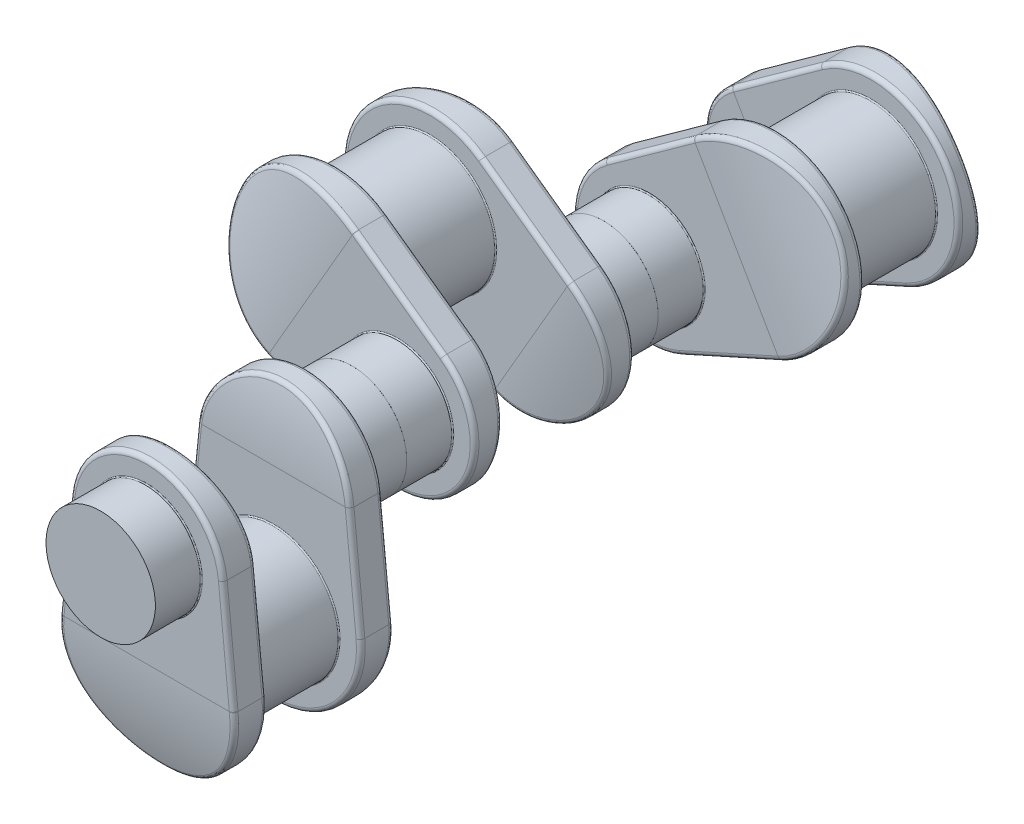
SolidWorks part; units mm, degrees
ref_plane "Front Plane" through (0, 0, 0) normal (0, 0, 1) x (1, 0, 0)
ref_plane "Top Plane" through (0, 0, 0) normal (0, 1, 0) x (1, 0, 0)
ref_plane "Right Plane" through (0, 0, 0) normal (1, 0, 0) x (0, 0, -1)
sketch "Sketch1" plane through (0, 0, 0) normal (0, 0, 1) x (1, 0, 0)
  circle A0 centre (0, 0) radius 38.1
extrude "Boss-Extrude1" add sketch "Sketch1" along normal blind 27.3
sketch "Sketch3" plane through (0, 0, 27.3) normal (0, 0, 1) x (1, 0, 0)
  line L0 (-44.2272, 67.945) -> (-50.5454, 5.08)
  line L1 (44.2272, 67.945) -> (50.5454, 5.08)
  arc A0 (-50.5454, 5.08) -> (50.5454, 5.08) centre (0, 0) ccw
  arc A1 (44.2272, 67.945) -> (-44.2272, 67.945) centre (0, 63.5) ccw
  circle A2 centre (0, 0) radius 38.1 construction
  dimension "D1" = 12.7
  dimension "D3" = 88.9
  dimension "D2" = 63.5
extrude "Boss-Extrude2" add sketch "Sketch3" along normal blind 19
sketch "Sketch4" plane through (0, 0, 46.3) normal (0, 0, 1) x (1, 0, 0)
  circle A0 centre (0, 63.5) radius 31.75
  dimension "D1" = 63.5
extrude "Boss-Extrude3" add sketch "Sketch4" along normal blind 26.67
sketch "Sketch7" plane through (0, 0, 0) normal (1, 0, 0) x (0, 0, -1)
  line L0 (-46.3, -50.8) -> (-27.3, -50.8) construction
  line L1 (-46.3, 5.08) -> (-70.3889, 5.08)
  line L2 (-70.3889, 5.08) -> (-70.3889, -50.8)
  line L3 (-70.3889, -50.8) -> (-36.8, -50.8)
  arc A0 (-46.3, 5.08) -> (-36.8, -50.8) centre (122.7, 5.0637) ccw
  dimension "D1" = 169
extrude "Cut-Extrude1" cut sketch "Sketch7" against normal mid plane 1000
sketch "Sketch8" plane through (0, 0, 0) normal (1, 0, 0) x (0, 0, -1)
  line L0 (-27.3, 107.95) -> (-46.3, 107.95) construction
  line L1 (-32.3, 107.95) -> (-15.8442, 107.95)
  line L2 (-15.8442, 107.95) -> (-15.8442, 67.945)
  line L3 (-15.8442, 67.945) -> (-27.3, 67.945)
  arc A0 (-27.3, 67.945) -> (-32.3, 107.95) centre (-196.2981, 67.1378) ccw
  dimension "D1" = 5
  dimension "D2" = 169
extrude "Cut-Extrude2" cut sketch "Sketch8" against normal mid plane 1000
fillet "Fillet1" radius 2.54 10 edges at (-47.3863, 36.5125, 27.3) (0, -50.8, 27.3) (50.5462, 5.0718, 46.3) (0.2715, -50.7993, 36.8003) (-50.5462, 5.0718, 46.3) (-47.3863, 36.5125, 46.3) (0, 107.95, 46.3) (5.8292, 107.5661, 32.2049) (47.3863, 36.5125, 27.3) (47.3863, 36.5125, 46.3)
fillet "Fillet2" radius 0.64 2 edges at (38.1, 0, 27.3) (31.75, 63.5, 46.3)
mirror "Mirror1" about plane through (0, 0, 0) normal (0, 0, 1) of bodies 106
pattern_linear "LPattern1" count 3 spacing 145.96 along (0, 0, -1) of bodies 107
ref_axis "Axis1" through (0, 63.5, 146.7602) along (0, 0, -1)
move or copy body "Body-Move/Copy1" bodies to move or copy 108 copy no rotation origin (0, 63.5, 0) rotation axis (0, 0, -1) rotation angle 120
move or copy body "Body-Move/Copy2" bodies to move or copy 109 copy no rotation origin (0, 63.5, 0) rotation axis (0, 0, 1) rotation angle 120
